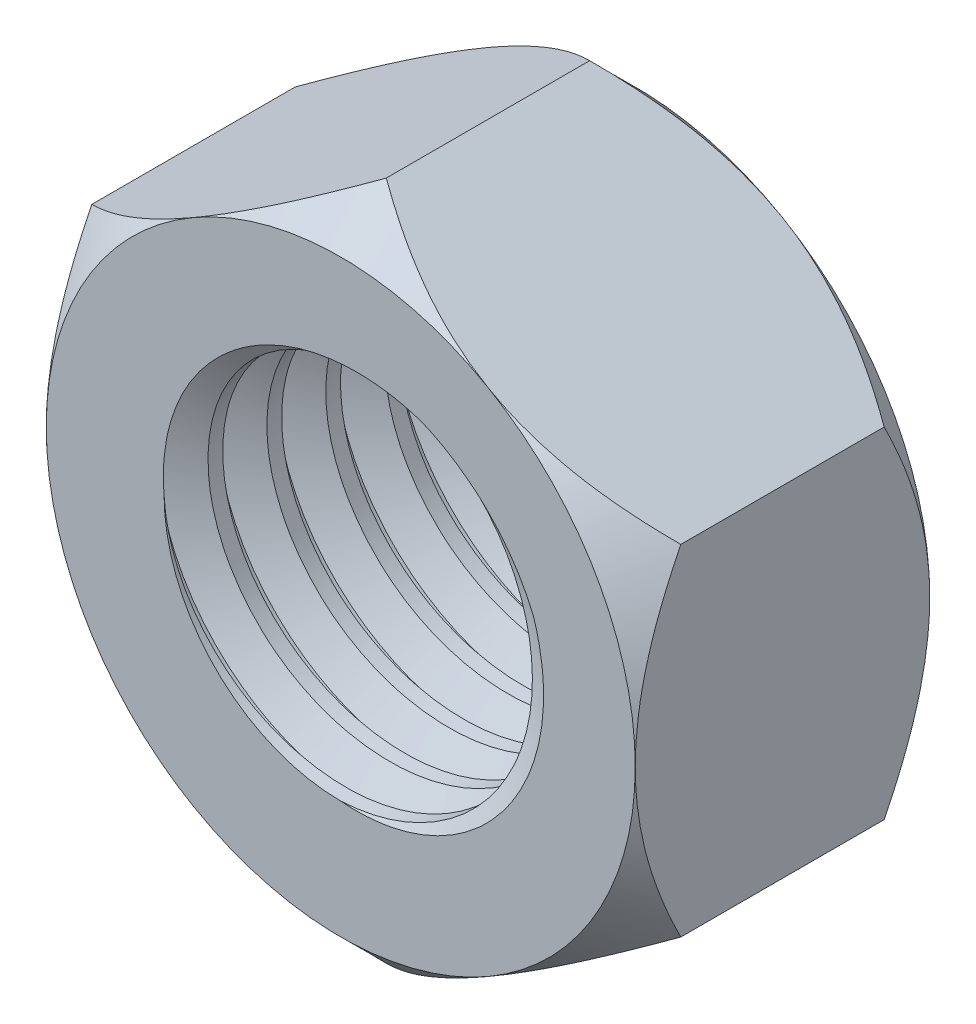
SolidWorks part; units mm, degrees
ref_plane "Front Plane" through (0, 0, 0) normal (0, 0, 1) x (1, 0, 0)
ref_plane "Top Plane" through (0, 0, 0) normal (0, 1, 0) x (1, 0, 0)
ref_plane "Right Plane" through (0, 0, 0) normal (1, 0, 0) x (0, 0, -1)
sketch "Sketch1" plane through (0, 0, 0) normal (0, 0, 1) x (1, 0, 0)
  line L1 (5, -2.8868) -> (5, 2.8868)
  line L2 (5, 2.8868) -> (0, 5.7735)
  line L3 (0, 5.7735) -> (-5, 2.8868)
  line L4 (-5, 2.8868) -> (-5, -2.8868)
  line L5 (-5, -2.8868) -> (0, -5.7735)
  line L6 (0, -5.7735) -> (5, -2.8868)
  circle A0 centre (0, 0) radius 5 construction
  circle A1 centre (0, 0) radius 3
  dimension "D1" = 10
  dimension "D2" = 6
extrude "Boss-Extrude2" add sketch "Sketch1" along normal mid plane 5 contours A1 | L5 L6 L1 L2 L3 L4 A1
sketch "Sketch2" plane through (0, 0, 2.5) normal (0, 0, 1) x (1, 0, 0)
  circle A0 centre (0, 0) radius 3
  dimension "D1" = 6
extrude "Cut-Extrude2" cut sketch "Sketch2" against normal through all
thread "Thread2" start angle 0, offset 2, length 26, pitch 1, diameter 6
ref_plane "Plane2" through (-3, 0, 4.5) normal (0, -1, 0) x (-1, 0, 0)
sketch "Thread Profile2" plane through (-3, 0, 4.5) normal (0, -1, 0) x (-1, 0, 0)
  line L0 (0, 0) -> (0, 1) construction
  line L1 (0, 0) -> (0.5413, 0.3125)
  line L2 (0.5413, 0.3125) -> (0.5413, 0.4375)
  line L3 (0.5413, 0.4375) -> (0, 0.75)
  line L4 (0.5413, 0.375) -> (0, 0.375) construction
  line L11 (0, 0) -> (0, 0.75)
  point P2 (0, 0)
  dimension "Pitch" = 1
  dimension "Profile_Angle" = 60
  dimension "Profile_Land" = 0.125
  dimension "Profile_Height" = 0.5413
sketch "Sketch3" plane through (0, 0, 2.5) normal (0, 0, 1) x (1, 0, 0)
  circle A0 centre (0, 0) radius 5
  dimension "D1" = 10
extrude "Cut-Extrude3" cut sketch "Sketch3" against normal blind 10 draft 45 flip side to cut
mirror "Mirror1" about plane through (0, 0, 0) normal (0, 0, 1) of "Cut-Extrude3"
